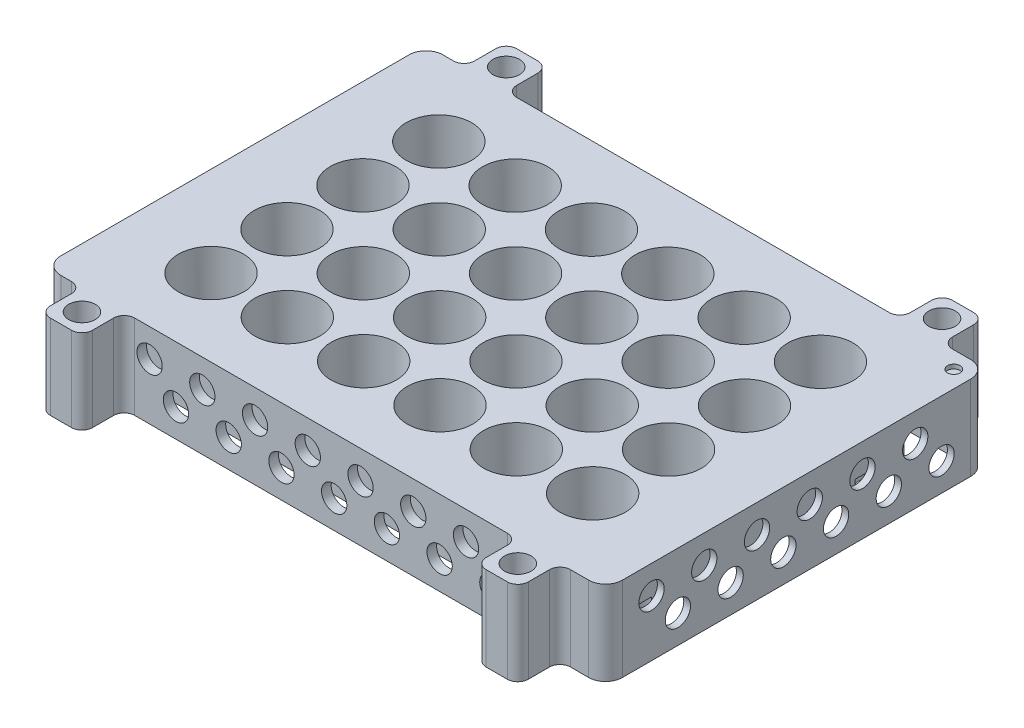
SolidWorks part; units mm, degrees
ref_plane "Front Plane" through (0, 0, 0) normal (0, 0, 1) x (1, 0, 0)
ref_plane "Top Plane" through (0, 0, 0) normal (0, 1, 0) x (1, 0, 0)
ref_plane "Right Plane" through (0, 0, 0) normal (1, 0, 0) x (0, 0, -1)
sketch "Sketch1" plane through (0, 0, 0) normal (0, 1, 0) x (1, 0, 0)
  line L1 (0, 0) -> (157.864, 0)
  line L2 (0, 0) -> (0, -90.551)
  line L3 (0, -90.551) -> (157.864, -90.551)
  line L4 (157.864, 0) -> (157.864, -90.551)
  dimension "D1" = 157.864
  dimension "D2" = 90.551
extrude "Boss-Extrude1" add sketch "Sketch1" along normal blind 24.5
sketch "Sketch39" plane through (0, 24.5, 0) normal (0, 1, 0) x (1, 0, 0)
  line L0 (37.0058, -18.5555) -> (30.949, -18.5555)
  line L1 (30.949, -18.5555) -> (30.4082, -19.0884)
  line L2 (30.4082, -19.0884) -> (30.4082, -25.1854)
  line L3 (30.4082, -25.1854) -> (37.0058, -25.1854)
  line L4 (37.0058, -18.5555) -> (37.0058, -25.1854)
  line L5 (30.4082, -25.1854) -> (37.0058, -18.5555) construction
  line L6 (55.0958, -11.3656) -> (49.039, -11.3656)
  line L7 (49.039, -11.3656) -> (48.4982, -11.8986)
  line L8 (48.4982, -11.8986) -> (48.4982, -17.9955)
  line L9 (48.4982, -17.9955) -> (55.0958, -17.9955)
  line L10 (55.0958, -11.3656) -> (55.0958, -17.9955)
  line L11 (48.4982, -17.9955) -> (55.0958, -11.3656) construction
  line L12 (73.1858, -11.3656) -> (67.129, -11.3656)
  line L13 (67.129, -11.3656) -> (66.5882, -11.8986)
  line L14 (66.5882, -11.8986) -> (66.5882, -17.9955)
  line L15 (66.5882, -17.9955) -> (73.1858, -17.9955)
  line L16 (73.1858, -11.3656) -> (73.1858, -17.9955)
  line L17 (66.5882, -17.9955) -> (73.1858, -11.3656) construction
  line L18 (91.2758, -11.3656) -> (85.219, -11.3656)
  line L19 (85.219, -11.3656) -> (84.6782, -11.8986)
  line L20 (84.6782, -11.8986) -> (84.6782, -17.9955)
  line L21 (84.6782, -17.9955) -> (91.2758, -17.9955)
  line L22 (91.2758, -11.3656) -> (91.2758, -17.9955)
  line L23 (84.6782, -17.9955) -> (91.2758, -11.3656) construction
  line L24 (109.3658, -11.3656) -> (103.309, -11.3656)
  line L25 (103.309, -11.3656) -> (102.7682, -11.8986)
  line L26 (102.7682, -11.8986) -> (102.7682, -17.9955)
  line L27 (102.7682, -17.9955) -> (109.3658, -17.9955)
  line L28 (109.3658, -11.3656) -> (109.3658, -17.9955)
  line L29 (102.7682, -17.9955) -> (109.3658, -11.3656) construction
  line L30 (127.4558, -11.3656) -> (121.399, -11.3656)
  line L31 (121.399, -11.3656) -> (120.8582, -11.8986)
  line L32 (120.8582, -11.8986) -> (120.8582, -17.9955)
  line L33 (120.8582, -17.9955) -> (127.4558, -17.9955)
  line L34 (127.4558, -11.3656) -> (127.4558, -17.9955)
  line L35 (120.8582, -17.9955) -> (127.4558, -11.3656) construction
  line L36 (55.0958, -29.3656) -> (49.039, -29.3656)
  line L37 (49.039, -29.3656) -> (48.4982, -29.8986)
  line L38 (48.4982, -29.8986) -> (48.4982, -35.9955)
  line L39 (48.4982, -35.9955) -> (55.0958, -35.9955)
  line L40 (55.0958, -29.3656) -> (55.0958, -35.9955)
  line L41 (48.4982, -35.9955) -> (55.0958, -29.3656) construction
  line L42 (73.1858, -29.3656) -> (67.129, -29.3656)
  line L43 (67.129, -29.3656) -> (66.5882, -29.8986)
  line L44 (66.5882, -29.8986) -> (66.5882, -35.9955)
  line L45 (66.5882, -35.9955) -> (73.1858, -35.9955)
  line L46 (73.1858, -29.3656) -> (73.1858, -35.9955)
  line L47 (66.5882, -35.9955) -> (73.1858, -29.3656) construction
  line L48 (91.2758, -29.3656) -> (85.219, -29.3656)
  line L49 (85.219, -29.3656) -> (84.6782, -29.8986)
  line L50 (84.6782, -29.8986) -> (84.6782, -35.9955)
  line L51 (84.6782, -35.9955) -> (91.2758, -35.9955)
  line L52 (91.2758, -29.3656) -> (91.2758, -35.9955)
  line L53 (84.6782, -35.9955) -> (91.2758, -29.3656) construction
  line L54 (109.3658, -29.3656) -> (103.309, -29.3656)
  line L55 (103.309, -29.3656) -> (102.7682, -29.8986)
  line L56 (102.7682, -29.8986) -> (102.7682, -35.9955)
  line L57 (102.7682, -35.9955) -> (109.3658, -35.9955)
  line L58 (109.3658, -29.3656) -> (109.3658, -35.9955)
  line L59 (102.7682, -35.9955) -> (109.3658, -29.3656) construction
  line L60 (127.4558, -29.3656) -> (121.399, -29.3656)
  line L61 (121.399, -29.3656) -> (120.8582, -29.8986)
  line L62 (120.8582, -29.8986) -> (120.8582, -35.9955)
  line L63 (120.8582, -35.9955) -> (127.4558, -35.9955)
  line L64 (127.4558, -29.3656) -> (127.4558, -35.9955)
  line L65 (120.8582, -35.9955) -> (127.4558, -29.3656) construction
  line L66 (55.0958, -47.3656) -> (49.039, -47.3656)
  line L67 (49.039, -47.3656) -> (48.4982, -47.8986)
  line L68 (48.4982, -47.8986) -> (48.4982, -53.9955)
  line L69 (48.4982, -53.9955) -> (55.0958, -53.9955)
  line L70 (55.0958, -47.3656) -> (55.0958, -53.9955)
  line L71 (48.4982, -53.9955) -> (55.0958, -47.3656) construction
  line L72 (73.1858, -47.3656) -> (67.129, -47.3656)
  line L73 (67.129, -47.3656) -> (66.5882, -47.8986)
  line L74 (66.5882, -47.8986) -> (66.5882, -53.9955)
  line L75 (66.5882, -53.9955) -> (73.1858, -53.9955)
  line L76 (73.1858, -47.3656) -> (73.1858, -53.9955)
  line L77 (66.5882, -53.9955) -> (73.1858, -47.3656) construction
  line L78 (91.2758, -47.3656) -> (85.219, -47.3656)
  line L79 (85.219, -47.3656) -> (84.6782, -47.8986)
  line L80 (84.6782, -47.8986) -> (84.6782, -53.9955)
  line L81 (84.6782, -53.9955) -> (91.2758, -53.9955)
  line L82 (91.2758, -47.3656) -> (91.2758, -53.9955)
  line L83 (84.6782, -53.9955) -> (91.2758, -47.3656) construction
  line L84 (109.3658, -47.3656) -> (103.309, -47.3656)
  line L85 (103.309, -47.3656) -> (102.7682, -47.8986)
  line L86 (102.7682, -47.8986) -> (102.7682, -53.9955)
  line L87 (102.7682, -53.9955) -> (109.3658, -53.9955)
  line L88 (109.3658, -47.3656) -> (109.3658, -53.9955)
  line L89 (102.7682, -53.9955) -> (109.3658, -47.3656) construction
  line L90 (127.4558, -47.3656) -> (121.399, -47.3656)
  line L91 (121.399, -47.3656) -> (120.8582, -47.8986)
  line L92 (120.8582, -47.8986) -> (120.8582, -53.9955)
  line L93 (120.8582, -53.9955) -> (127.4558, -53.9955)
  line L94 (127.4558, -47.3656) -> (127.4558, -53.9955)
  line L95 (120.8582, -53.9955) -> (127.4558, -47.3656) construction
  line L96 (55.0958, -65.3656) -> (49.039, -65.3656)
  line L97 (49.039, -65.3656) -> (48.4982, -65.8986)
  line L98 (48.4982, -65.8986) -> (48.4982, -71.9955)
  line L99 (48.4982, -71.9955) -> (55.0958, -71.9955)
  line L100 (55.0958, -65.3656) -> (55.0958, -71.9955)
  line L101 (48.4982, -71.9955) -> (55.0958, -65.3656) construction
  line L102 (73.1858, -65.3656) -> (67.129, -65.3656)
  line L103 (67.129, -65.3656) -> (66.5882, -65.8986)
  line L104 (66.5882, -65.8986) -> (66.5882, -71.9955)
  line L105 (66.5882, -71.9955) -> (73.1858, -71.9955)
  line L106 (73.1858, -65.3656) -> (73.1858, -71.9955)
  line L107 (66.5882, -71.9955) -> (73.1858, -65.3656) construction
  line L108 (91.2758, -65.3656) -> (85.219, -65.3656)
  line L109 (85.219, -65.3656) -> (84.6782, -65.8986)
  line L110 (84.6782, -65.8986) -> (84.6782, -71.9955)
  line L111 (84.6782, -71.9955) -> (91.2758, -71.9955)
  line L112 (91.2758, -65.3656) -> (91.2758, -71.9955)
  line L113 (84.6782, -71.9955) -> (91.2758, -65.3656) construction
  line L114 (109.3658, -65.3656) -> (103.309, -65.3656)
  line L115 (103.309, -65.3656) -> (102.7682, -65.8986)
  line L116 (102.7682, -65.8986) -> (102.7682, -71.9955)
  line L117 (102.7682, -71.9955) -> (109.3658, -71.9955)
  line L118 (109.3658, -65.3656) -> (109.3658, -71.9955)
  line L119 (102.7682, -71.9955) -> (109.3658, -65.3656) construction
  line L120 (127.4558, -65.3656) -> (121.399, -65.3656)
  line L121 (121.399, -65.3656) -> (120.8582, -65.8986)
  line L122 (120.8582, -65.8986) -> (120.8582, -71.9955)
  line L123 (120.8582, -71.9955) -> (127.4558, -71.9955)
  line L124 (127.4558, -65.3656) -> (127.4558, -71.9955)
  line L125 (120.8582, -71.9955) -> (127.4558, -65.3656) construction
  line L126 (37.0058, -29.3656) -> (30.949, -29.3656)
  line L127 (30.949, -29.3656) -> (30.4082, -29.8986)
  line L128 (30.4082, -29.8986) -> (30.4082, -35.9955)
  line L129 (30.4082, -35.9955) -> (37.0058, -35.9955)
  line L130 (37.0058, -29.3656) -> (37.0058, -35.9955)
  line L131 (30.4082, -35.9955) -> (37.0058, -29.3656) construction
  line L132 (37.0058, -47.3656) -> (30.949, -47.3656)
  line L133 (30.949, -47.3656) -> (30.4082, -47.8986)
  line L134 (30.4082, -47.8986) -> (30.4082, -53.9955)
  line L135 (30.4082, -53.9955) -> (37.0058, -53.9955)
  line L136 (37.0058, -47.3656) -> (37.0058, -53.9955)
  line L137 (30.4082, -53.9955) -> (37.0058, -47.3656) construction
  line L138 (37.0058, -65.3656) -> (30.949, -65.3656)
  line L139 (30.949, -65.3656) -> (30.4082, -65.8986)
  line L140 (30.4082, -65.8986) -> (30.4082, -71.9955)
  line L141 (30.4082, -71.9955) -> (37.0058, -71.9955)
  line L142 (37.0058, -65.3656) -> (37.0058, -71.9955)
  line L143 (30.4082, -71.9955) -> (37.0058, -65.3656) construction
  line L144 (37.0058, -11.3656) -> (30.949, -11.3656)
  line L145 (30.949, -11.3656) -> (30.4082, -11.8986)
  line L146 (30.4082, -11.8986) -> (30.4082, -17.9955)
  line L147 (30.4082, -17.9955) -> (37.0058, -17.9955)
  line L148 (37.0058, -11.3656) -> (37.0058, -17.9955)
  line L149 (30.4082, -17.9955) -> (37.0058, -11.3656) construction
  line L150 (48.4982, -25.1854) -> (55.0958, -25.1854)
  line L151 (55.0958, -18.5555) -> (55.0958, -25.1854)
  line L152 (55.0958, -18.5555) -> (49.039, -18.5555)
  line L153 (49.039, -18.5555) -> (48.4982, -19.0884)
  line L154 (48.4982, -19.0884) -> (48.4982, -25.1854)
  line L155 (48.4982, -25.1854) -> (55.0958, -18.5555) construction
  line L156 (66.5882, -25.1854) -> (73.1858, -25.1854)
  line L157 (73.1858, -18.5555) -> (73.1858, -25.1854)
  line L158 (73.1858, -18.5555) -> (67.129, -18.5555)
  line L159 (67.129, -18.5555) -> (66.5882, -19.0884)
  line L160 (66.5882, -19.0884) -> (66.5882, -25.1854)
  line L161 (66.5882, -25.1854) -> (73.1858, -18.5555) construction
  line L162 (84.6782, -25.1854) -> (91.2758, -25.1854)
  line L163 (91.2758, -18.5555) -> (91.2758, -25.1854)
  line L164 (91.2758, -18.5555) -> (85.219, -18.5555)
  line L165 (85.219, -18.5555) -> (84.6782, -19.0884)
  line L166 (84.6782, -19.0884) -> (84.6782, -25.1854)
  line L167 (84.6782, -25.1854) -> (91.2758, -18.5555) construction
  line L168 (102.7682, -25.1854) -> (109.3658, -25.1854)
  line L169 (109.3658, -18.5555) -> (109.3658, -25.1854)
  line L170 (109.3658, -18.5555) -> (103.309, -18.5555)
  line L171 (103.309, -18.5555) -> (102.7682, -19.0884)
  line L172 (102.7682, -19.0884) -> (102.7682, -25.1854)
  line L173 (102.7682, -25.1854) -> (109.3658, -18.5555) construction
  line L174 (120.8582, -25.1854) -> (127.4558, -25.1854)
  line L175 (127.4558, -18.5555) -> (127.4558, -25.1854)
  line L176 (127.4558, -18.5555) -> (121.399, -18.5555)
  line L177 (121.399, -18.5555) -> (120.8582, -19.0884)
  line L178 (120.8582, -19.0884) -> (120.8582, -25.1854)
  line L179 (120.8582, -25.1854) -> (127.4558, -18.5555) construction
  line L180 (48.4982, -43.1854) -> (55.0958, -43.1854)
  line L181 (55.0958, -36.5555) -> (55.0958, -43.1854)
  line L182 (55.0958, -36.5555) -> (49.039, -36.5555)
  line L183 (49.039, -36.5555) -> (48.4982, -37.0884)
  line L184 (48.4982, -37.0884) -> (48.4982, -43.1854)
  line L185 (48.4982, -43.1854) -> (55.0958, -36.5555) construction
  line L186 (66.5882, -43.1854) -> (73.1858, -43.1854)
  line L187 (73.1858, -36.5555) -> (73.1858, -43.1854)
  line L188 (73.1858, -36.5555) -> (67.129, -36.5555)
  line L189 (67.129, -36.5555) -> (66.5882, -37.0884)
  line L190 (66.5882, -37.0884) -> (66.5882, -43.1854)
  line L191 (66.5882, -43.1854) -> (73.1858, -36.5555) construction
  line L192 (84.6782, -43.1854) -> (91.2758, -43.1854)
  line L193 (91.2758, -36.5555) -> (91.2758, -43.1854)
  line L194 (91.2758, -36.5555) -> (85.219, -36.5555)
  line L195 (85.219, -36.5555) -> (84.6782, -37.0884)
  line L196 (84.6782, -37.0884) -> (84.6782, -43.1854)
  line L197 (84.6782, -43.1854) -> (91.2758, -36.5555) construction
  line L198 (102.7682, -43.1854) -> (109.3658, -43.1854)
  line L199 (109.3658, -36.5555) -> (109.3658, -43.1854)
  line L200 (109.3658, -36.5555) -> (103.309, -36.5555)
  line L201 (103.309, -36.5555) -> (102.7682, -37.0884)
  line L202 (102.7682, -37.0884) -> (102.7682, -43.1854)
  line L203 (102.7682, -43.1854) -> (109.3658, -36.5555) construction
  line L204 (120.8582, -43.1854) -> (127.4558, -43.1854)
  line L205 (127.4558, -36.5555) -> (127.4558, -43.1854)
  line L206 (127.4558, -36.5555) -> (121.399, -36.5555)
  line L207 (121.399, -36.5555) -> (120.8582, -37.0884)
  line L208 (120.8582, -37.0884) -> (120.8582, -43.1854)
  line L209 (120.8582, -43.1854) -> (127.4558, -36.5555) construction
  line L210 (48.4982, -61.1854) -> (55.0958, -61.1854)
  line L211 (55.0958, -54.5555) -> (55.0958, -61.1854)
  line L212 (55.0958, -54.5555) -> (49.039, -54.5555)
  line L213 (49.039, -54.5555) -> (48.4982, -55.0884)
  line L214 (48.4982, -55.0884) -> (48.4982, -61.1854)
  line L215 (48.4982, -61.1854) -> (55.0958, -54.5555) construction
  line L216 (66.5882, -61.1854) -> (73.1858, -61.1854)
  line L217 (73.1858, -54.5555) -> (73.1858, -61.1854)
  line L218 (73.1858, -54.5555) -> (67.129, -54.5555)
  line L219 (67.129, -54.5555) -> (66.5882, -55.0884)
  line L220 (66.5882, -55.0884) -> (66.5882, -61.1854)
  line L221 (66.5882, -61.1854) -> (73.1858, -54.5555) construction
  line L222 (84.6782, -61.1854) -> (91.2758, -61.1854)
  line L223 (91.2758, -54.5555) -> (91.2758, -61.1854)
  line L224 (91.2758, -54.5555) -> (85.219, -54.5555)
  line L225 (85.219, -54.5555) -> (84.6782, -55.0884)
  line L226 (84.6782, -55.0884) -> (84.6782, -61.1854)
  line L227 (84.6782, -61.1854) -> (91.2758, -54.5555) construction
  line L228 (102.7682, -61.1854) -> (109.3658, -61.1854)
  line L229 (109.3658, -54.5555) -> (109.3658, -61.1854)
  line L230 (109.3658, -54.5555) -> (103.309, -54.5555)
  line L231 (103.309, -54.5555) -> (102.7682, -55.0884)
  line L232 (102.7682, -55.0884) -> (102.7682, -61.1854)
  line L233 (102.7682, -61.1854) -> (109.3658, -54.5555) construction
  line L234 (120.8582, -61.1854) -> (127.4558, -61.1854)
  line L235 (127.4558, -54.5555) -> (127.4558, -61.1854)
  line L236 (127.4558, -54.5555) -> (121.399, -54.5555)
  line L237 (121.399, -54.5555) -> (120.8582, -55.0884)
  line L238 (120.8582, -55.0884) -> (120.8582, -61.1854)
  line L239 (120.8582, -61.1854) -> (127.4558, -54.5555) construction
  line L240 (48.4982, -79.1854) -> (55.0958, -79.1854)
  line L241 (55.0958, -72.5555) -> (55.0958, -79.1854)
  line L242 (55.0958, -72.5555) -> (49.039, -72.5555)
  line L243 (49.039, -72.5555) -> (48.4982, -73.0884)
  line L244 (48.4982, -73.0884) -> (48.4982, -79.1854)
  line L245 (48.4982, -79.1854) -> (55.0958, -72.5555) construction
  line L246 (66.5882, -79.1854) -> (73.1858, -79.1854)
  line L247 (73.1858, -72.5555) -> (73.1858, -79.1854)
  line L248 (73.1858, -72.5555) -> (67.129, -72.5555)
  line L249 (67.129, -72.5555) -> (66.5882, -73.0884)
  line L250 (66.5882, -73.0884) -> (66.5882, -79.1854)
  line L251 (66.5882, -79.1854) -> (73.1858, -72.5555) construction
  line L252 (84.6782, -79.1854) -> (91.2758, -79.1854)
  line L253 (91.2758, -72.5555) -> (91.2758, -79.1854)
  line L254 (91.2758, -72.5555) -> (85.219, -72.5555)
  line L255 (85.219, -72.5555) -> (84.6782, -73.0884)
  line L256 (84.6782, -73.0884) -> (84.6782, -79.1854)
  line L257 (84.6782, -79.1854) -> (91.2758, -72.5555) construction
  line L258 (102.7682, -79.1854) -> (109.3658, -79.1854)
  line L259 (109.3658, -72.5555) -> (109.3658, -79.1854)
  line L260 (109.3658, -72.5555) -> (103.309, -72.5555)
  line L261 (103.309, -72.5555) -> (102.7682, -73.0884)
  line L262 (102.7682, -73.0884) -> (102.7682, -79.1854)
  line L263 (102.7682, -79.1854) -> (109.3658, -72.5555) construction
  line L264 (120.8582, -79.1854) -> (127.4558, -79.1854)
  line L265 (127.4558, -72.5555) -> (127.4558, -79.1854)
  line L266 (127.4558, -72.5555) -> (121.399, -72.5555)
  line L267 (121.399, -72.5555) -> (120.8582, -73.0884)
  line L268 (120.8582, -73.0884) -> (120.8582, -79.1854)
  line L269 (120.8582, -79.1854) -> (127.4558, -72.5555) construction
  line L270 (30.4082, -43.1854) -> (37.0058, -43.1854)
  line L271 (37.0058, -36.5555) -> (37.0058, -43.1854)
  line L272 (37.0058, -36.5555) -> (30.949, -36.5555)
  line L273 (30.949, -36.5555) -> (30.4082, -37.0884)
  line L274 (30.4082, -37.0884) -> (30.4082, -43.1854)
  line L275 (30.4082, -43.1854) -> (37.0058, -36.5555) construction
  line L276 (30.4082, -61.1854) -> (37.0058, -61.1854)
  line L277 (37.0058, -54.5555) -> (37.0058, -61.1854)
  line L278 (37.0058, -54.5555) -> (30.949, -54.5555)
  line L279 (30.949, -54.5555) -> (30.4082, -55.0884)
  line L280 (30.4082, -55.0884) -> (30.4082, -61.1854)
  line L281 (30.4082, -61.1854) -> (37.0058, -54.5555) construction
  line L282 (30.4082, -79.1854) -> (37.0058, -79.1854)
  line L283 (37.0058, -72.5555) -> (37.0058, -79.1854)
  line L284 (37.0058, -72.5555) -> (30.949, -72.5555)
  line L285 (30.949, -72.5555) -> (30.4082, -73.0884)
  line L286 (30.4082, -73.0884) -> (30.4082, -79.1854)
  line L287 (30.4082, -79.1854) -> (37.0058, -72.5555) construction
  line L288 (127.4558, -25.1854) -> (157.864, -25.1854) construction
  line L289 (30.4082, -79.1854) -> (0, -79.1854) construction
  line L290 (0, 0) -> (0, -90.551) construction
  line L291 (30.4082, -79.1854) -> (30.4082, -90.551) construction
  line L292 (0, -90.551) -> (157.864, -90.551) construction
  line L293 (127.4558, -11.3656) -> (127.4558, 0) construction
  line L294 (157.864, 0) -> (0, 0) construction
  line L295 (127.4558, -11.3656) -> (157.864, -11.3656) construction
  line L296 (157.864, -90.551) -> (157.864, 0) construction
  point P0 (33.707, -21.8704)
  point P2 (33.707, -14.6806)
  point P12 (51.797, -14.6806)
  point P18 (69.887, -14.6806)
  point P24 (87.977, -14.6806)
  point P30 (106.067, -14.6806)
  point P36 (124.157, -14.6806)
  point P42 (51.797, -32.6806)
  point P48 (69.887, -32.6806)
  point P54 (87.977, -32.6806)
  point P60 (106.067, -32.6806)
  point P66 (124.157, -32.6806)
  point P72 (51.797, -50.6806)
  point P78 (69.887, -50.6806)
  point P84 (87.977, -50.6806)
  point P90 (106.067, -50.6806)
  point P96 (124.157, -50.6806)
  point P102 (51.797, -68.6806)
  point P108 (69.887, -68.6806)
  point P114 (87.977, -68.6806)
  point P120 (106.067, -68.6806)
  point P126 (124.157, -68.6806)
  point P132 (33.707, -32.6806)
  point P138 (33.707, -50.6806)
  point P144 (33.707, -68.6806)
  point P153 (51.797, -21.8704)
  point P159 (69.887, -21.8704)
  point P165 (87.977, -21.8704)
  point P171 (106.067, -21.8704)
  point P177 (124.157, -21.8704)
  point P183 (51.797, -39.8704)
  point P189 (69.887, -39.8704)
  point P195 (87.977, -39.8704)
  point P201 (106.067, -39.8704)
  point P207 (124.157, -39.8704)
  point P213 (51.797, -57.8704)
  point P219 (69.887, -57.8704)
  point P225 (87.977, -57.8704)
  point P231 (106.067, -57.8704)
  point P237 (124.157, -57.8704)
  point P243 (51.797, -75.8704)
  point P249 (69.887, -75.8704)
  point P255 (87.977, -75.8704)
  point P261 (106.067, -75.8704)
  point P267 (124.157, -75.8704)
  point P273 (33.707, -39.8704)
  point P279 (33.707, -57.8704)
  point P285 (33.707, -75.8704)
  dimension "D2" = 6.0568
  dimension "D3" = 6.0969
  dimension "D4" = 6.5976
  dimension "D5" = 6.6299
  dimension "D6" = 0.7593
  dimension "D7" = 6
  dimension "D8" = 4
  dimension "D9" = 0.56
  dimension "D10" = 6.0568
  dimension "D11" = 6.0969
  dimension "D12" = 6.6299
  dimension "D13" = 6.5976
  dimension "D14" = 0.7593
  dimension "D15" = 6
  dimension "D16" = 4
extrude "Cut-Extrude30" cut sketch "Sketch39" against normal up to surface (24.5 mm away) up to face at (78.932, 0, 45.2755)
sketch "Sketch7" plane through (0, 0, 0) normal (0, -1, 0) x (1, 0, 0)
  line L0 (124.157, 18.2755) -> (157.864, 18.2755) construction
  line L1 (157.864, 90.551) -> (157.864, 0) construction
  line L2 (124.157, 18.2755) -> (124.157, 0) construction
  line L3 (157.864, 0) -> (0, 0) construction
  line L4 (33.707, 18.2755) -> (0, 18.2755) construction
  line L5 (0, 0) -> (0, 90.551) construction
  line L6 (33.707, 72.2755) -> (33.707, 90.551) construction
  line L7 (0, 90.551) -> (157.864, 90.551) construction
  line L8 (33.707, 72.2755) -> (33.707, 90.551) construction
  circle A0 centre (33.707, 72.2755) radius 7.75
  circle A2 centre (51.797, 72.2755) radius 7.75
  circle A3 centre (69.887, 72.2755) radius 7.75
  circle A4 centre (87.977, 72.2755) radius 7.75
  circle A5 centre (106.067, 72.2755) radius 7.75
  circle A6 centre (124.157, 72.2755) radius 7.75
  circle A7 centre (51.797, 54.2755) radius 7.75
  circle A8 centre (69.887, 54.2755) radius 7.75
  circle A9 centre (87.977, 54.2755) radius 7.75
  circle A10 centre (106.067, 54.2755) radius 7.75
  circle A11 centre (124.157, 54.2755) radius 7.75
  circle A12 centre (51.797, 36.2755) radius 7.75
  circle A13 centre (69.887, 36.2755) radius 7.75
  circle A14 centre (87.977, 36.2755) radius 7.75
  circle A15 centre (106.067, 36.2755) radius 7.75
  circle A16 centre (124.157, 36.2755) radius 7.75
  circle A17 centre (51.797, 18.2755) radius 7.75
  circle A18 centre (69.887, 18.2755) radius 7.75
  circle A19 centre (87.977, 18.2755) radius 7.75
  circle A20 centre (106.067, 18.2755) radius 7.75
  circle A21 centre (124.157, 18.2755) radius 7.75
  circle A22 centre (33.707, 54.2755) radius 7.75
  circle A23 centre (33.707, 36.2755) radius 7.75
  circle A24 centre (33.707, 18.2755) radius 7.75
  dimension "D1" = 15.5
  dimension "D6" = 18
  dimension "D3" = 18.09
  dimension "D4" = 18
  dimension "D5" = 18.09
  dimension "D7" = 6
  dimension "D8" = 4
extrude "Cut-Extrude5" cut sketch "Sketch7" along normal blind 17 from surface starting at face at (33.1554, 24.5, 75.314)
sketch "Sketch23" plane through (0, 24.5, 0) normal (0, 1, 0) x (1, 0, 0)
  line L0 (0, -90.551) -> (157.864, -90.551) construction
  line L1 (143.5751, -88.6374) -> (14.2889, -88.6374)
  line L2 (143.5751, -88.6374) -> (143.5751, -1.9136)
  line L3 (143.5751, -1.9136) -> (14.2889, -1.9136)
  line L4 (14.2889, -88.6374) -> (14.2889, -1.9136)
  line L5 (134.6751, -82.6374) -> (23.1889, -82.6374)
  line L6 (134.6751, -82.6374) -> (134.6751, -7.9136)
  line L7 (134.6751, -7.9136) -> (23.1889, -7.9136)
  line L8 (23.1889, -82.6374) -> (23.1889, -7.9136)
  line L9 (157.864, -90.551) -> (157.864, 0) construction
  line L10 (157.864, 0) -> (0, 0) construction
  line L11 (0, 0) -> (0, -90.551) construction
  point P8 (157.864, -45.2755)
  point P17 (0, -45.2755)
  dimension "D1" = 129.2861
  dimension "D2" = 8.9
  dimension "D3" = 8.9
  dimension "D4" = 6
  dimension "D5" = 6
  dimension "D6" = 14.2889
  dimension "D8" = 1.9136
  dimension "D9" = 86.7238
  dimension "D10" = 1.9136
  dimension "D11" = 14.2889
extrude "Cut-Extrude21" cut sketch "Sketch23" against normal blind 4.5
fillet "Fillet7" radius 1 4 edges at (134.6751, 22.25, 7.9136) (23.1889, 22.25, 7.9136) (23.1889, 22.25, 82.6374) (134.6751, 22.25, 82.6374)
fillet "Fillet8" radius 2.75 4 edges at (143.5751, 22.25, 1.9136) (14.2889, 22.25, 1.9136) (14.2889, 22.25, 88.6374) (143.5751, 22.25, 88.6374)
sketch "Sketch26" plane through (0, 24.5, 0) normal (0, 1, 0) x (1, 0, 0)
  line L1 (18.0889, -82.6374) -> (134.6751, -82.6374)
  line L2 (18.0889, -82.6374) -> (18.0889, -7.9136)
  line L3 (18.0889, -7.9136) -> (134.6751, -7.9136)
  line L4 (134.6751, -82.6374) -> (134.6751, -7.9136)
  dimension "D1" = 0
  dimension "D2" = 0
  dimension "D3" = 1
  dimension "D4" = 0
extrude "Cut-Extrude22" cut sketch "Sketch26" against normal blind 3
sketch "Sketch29" plane through (0, 24.5, 0) normal (0, 1, 0) x (1, 0, 0)
  line L0 (157.864, 0) -> (0, 0) construction
  line L1 (157.864, -90.551) -> (145.4887, -90.551)
  line L2 (157.864, -90.551) -> (157.864, 0)
  line L3 (157.864, 0) -> (145.4887, 0)
  line L4 (145.4887, -90.551) -> (145.4887, 0)
  line L6 (0, -90.551) -> (12.3753, -90.551)
  line L7 (0, -90.551) -> (0, 0)
  line L8 (0, 0) -> (12.3753, 0)
  line L9 (12.3753, -90.551) -> (12.3753, 0)
  dimension "D2" = 1.9136
  dimension "D3" = 1.9136
extrude "Cut-Extrude25" cut sketch "Sketch29" against normal through all
fillet "Fillet9" radius 4 4 edges at (12.3753, 12.25, 90.551) (145.4887, 12.25, 90.551) (145.4887, 12.25, 0) (12.3753, 12.25, 0)
sketch "Sketch30" plane through (0, 0, 0) normal (0, -1, 0) x (1, 0, 0)
  line L0 (141.4887, 0) -> (16.3753, 0) construction
  line L1 (134.6936, 0) -> (124.6936, 0)
  line L2 (134.6936, 0) -> (134.6936, -10)
  line L3 (134.6936, -10) -> (124.6936, -10)
  line L4 (124.6936, 0) -> (124.6936, -10)
  line L5 (16.3753, 90.551) -> (141.4887, 90.551) construction
  line L6 (21.3936, 0) -> (31.3936, 0)
  line L7 (21.3936, 0) -> (21.3936, -10)
  line L8 (21.3936, -10) -> (31.3936, -10)
  line L9 (31.3936, 0) -> (31.3936, -10)
  line L10 (134.6936, 90.551) -> (124.6936, 90.551)
  line L11 (134.6936, 90.551) -> (134.6936, 100.551)
  line L12 (134.6936, 100.551) -> (124.6936, 100.551)
  line L13 (124.6936, 90.551) -> (124.6936, 100.551)
  line L14 (124.6936, -10) -> (31.3936, -10) construction
  line L15 (21.3936, 90.551) -> (31.3936, 90.551)
  line L16 (21.3936, 90.551) -> (21.3936, 100.551)
  line L17 (21.3936, 100.551) -> (31.3936, 100.551)
  line L18 (31.3936, 90.551) -> (31.3936, 100.551)
  line L19 (124.6936, 100.551) -> (31.3936, 100.551) construction
  line L20 (31.3936, -10) -> (21.3936, 0) construction
  line L22 (33.707, 0) -> (31.3936, 0) construction
  line L23 (21.3936, 90.551) -> (16.3753, 90.551) construction
  line L24 (33.707, 72.2755) -> (33.707, 18.2755) construction
  line L25 (33.707, 18.2755) -> (33.707, 0) construction
  line L26 (21.3936, -10) -> (31.3936, 0) construction
  line L27 (33.707, 72.2755) -> (33.707, 90.551) construction
  line L28 (31.3936, 90.551) -> (21.3936, 100.551) construction
  line L29 (21.3936, 90.551) -> (31.3936, 100.551) construction
  point P21 (26.3936, -5)
  point P25 (26.3936, 95.551)
  dimension "D1" = 10
  dimension "D2" = 93.3
  dimension "D3" = 7.3134
  dimension "D4" = 7.3134
extrude "Boss-Extrude2" add sketch "Sketch30" against normal through all
sketch "Sketch31" plane through (0, 24.5, 0) normal (0, 1, 0) x (1, 0, 0)
  line L0 (21.3936, 10) -> (31.3936, 0) construction
  line L1 (31.3936, 0) -> (21.3936, 0) construction
  line L2 (21.3936, 0) -> (31.3936, 10) construction
  line L3 (124.6936, 10) -> (134.6936, 0) construction
  line L4 (134.6936, 0) -> (124.6936, 0) construction
  line L5 (124.6936, 0) -> (134.6936, 10) construction
  line L6 (124.6936, -90.551) -> (134.6936, -100.551) construction
  line L7 (134.6936, -100.551) -> (124.6936, -100.551) construction
  line L8 (124.6936, -100.551) -> (134.6936, -90.551) construction
  line L9 (21.3936, -90.551) -> (31.3936, -100.551) construction
  line L10 (31.3936, -100.551) -> (21.3936, -100.551) construction
  line L11 (21.3936, -100.551) -> (31.3936, -90.551) construction
  circle A0 centre (26.3936, 5) radius 3.15
  circle A1 centre (129.6936, 5) radius 3.15
  circle A2 centre (26.3936, -95.551) radius 3.15
  circle A3 centre (129.6936, -95.551) radius 3.15
  dimension "D1" = 6.3
extrude "Cut-Extrude26" cut sketch "Sketch31" against normal through all
fillet "Fillet10" radius 2.5 16 edges at (21.3936, 12.25, 100.551) (124.6936, 12.25, 100.551) (31.3936, 12.25, 100.551) (134.6936, 12.25, 100.551) (134.6936, 12.25, -10) (124.6936, 12.25, -10) (31.3936, 12.25, -10) (21.3936, 12.25, -10) (21.3936, 12.25, 90.551) (31.3936, 12.25, 90.551) (124.6936, 12.25, 90.551) (134.6936, 12.25, 90.551) (134.6936, 12.25, 0) (124.6936, 12.25, 0) (31.3936, 12.25, 0) (21.3936, 12.25, 0)
sketch "Sketch35" plane through (0, 21.5, 0) normal (0, 1, 0) x (1, 0, 0)
  line L0 (33.707, -54.2755) -> (51.797, -72.2755) construction
  line L1 (51.797, -72.2755) -> (33.707, -72.2755) construction
  line L2 (33.707, -72.2755) -> (51.797, -54.2755) construction
  line L3 (106.067, -18.2755) -> (124.157, -36.2755) construction
  line L4 (124.157, -36.2755) -> (106.067, -36.2755) construction
  line L5 (106.067, -36.2755) -> (124.157, -18.2755) construction
  circle A2 centre (115.112, -27.2755) radius 1.4
  circle A3 centre (42.752, -63.2755) radius 1.4
  dimension "D1" = 2.8
extrude "Boss-Extrude3" add sketch "Sketch35" along normal blind 0.75
sketch "Sketch37" plane through (0, 24.5, 0) normal (0, 1, 0) x (1, 0, 0)
  line L1 (-21.3738, -118.5753) -> (214.6608, -118.5753)
  line L2 (-21.3738, -118.5753) -> (-21.3738, 29.3482)
  line L3 (-21.3738, 29.3482) -> (214.6608, 29.3482)
  line L4 (214.6608, -118.5753) -> (214.6608, 29.3482)
extrude "Cut-Extrude29" cut sketch "Sketch37" against normal blind 4.5
sketch "Sketch36" plane through (0, 0, 0) normal (0, -1, 0) x (1, 0, 0)
  line L0 (23.3443, 83.2148) -> (23.3443, 88.2648) construction
  line L1 (14.5962, 88.2648) -> (143.8803, 88.2648)
  line L2 (14.5962, 88.2648) -> (14.5962, 2.0921)
  line L3 (14.5962, 2.0921) -> (143.8803, 2.0921)
  line L4 (143.8803, 88.2648) -> (143.8803, 2.0921)
  line L5 (23.3443, 83.2148) -> (135.1322, 83.2148)
  line L6 (23.3443, 83.2148) -> (23.3443, 7.142)
  line L7 (23.3443, 7.142) -> (135.1322, 7.142)
  line L8 (135.1322, 83.2148) -> (135.1322, 7.142)
  line L9 (23.3443, 83.2148) -> (14.5962, 83.2148) construction
  line L10 (135.1322, 7.142) -> (143.8803, 7.142) construction
  line L11 (135.1322, 7.142) -> (135.1322, 2.0921) construction
extrude "Cut-Extrude28" cut sketch "Sketch36" against normal blind 17
fillet "Fillet11" radius 4 4 edges at (135.1322, 8.5, 83.2148) (23.3443, 8.5, 83.2148) (23.3443, 8.5, 7.142) (135.1322, 8.5, 7.142)
fillet "Fillet12" radius 4 4 edges at (143.8803, 8.5, 88.2648) (14.5962, 8.5, 88.2648) (14.5962, 8.5, 2.0921) (143.8803, 8.5, 2.0921)
sketch "Sketch42" plane through (0, 0, 0) normal (0, -1, 0) x (1, 0, 0)
  line L0 (22.1833, 72.1734) -> (22.1833, 18.1834) construction
  line L1 (22.1833, 18.1834) -> (136.2933, 18.1834) construction
  line L2 (136.2933, 18.1834) -> (136.2933, 72.1734) construction
  line L3 (136.2933, 72.1734) -> (22.1833, 72.1734) construction
  line L4 (22.1833, 72.1734) -> (14.5962, 72.1734) construction
  line L5 (14.5962, 84.2648) -> (14.5962, 6.0921) construction
  line L6 (22.1833, 72.1734) -> (22.1833, 88.2648) construction
  line L7 (139.8803, 88.2648) -> (18.5962, 88.2648) construction
  line L8 (136.2933, 72.1734) -> (143.8803, 72.1734) construction
  line L9 (143.8803, 6.0921) -> (143.8803, 84.2648) construction
  line L10 (136.2933, 18.1834) -> (136.2933, 2.0921) construction
  line L11 (18.5962, 2.0921) -> (139.8803, 2.0921) construction
  circle A0 centre (22.1833, 72.1734) radius 3.1
  circle A1 centre (22.1833, 18.1834) radius 3.1
  circle A2 centre (136.2933, 18.1834) radius 3.1
  circle A3 centre (136.2933, 72.1734) radius 3.1
  dimension "D1" = 6.2
  dimension "D2" = 114.11
  dimension "D3" = 53.99
extrude "Cut-Extrude31" cut sketch "Sketch42" against normal blind 2.75
sketch "Sketch43" plane through (0, 20, 0) normal (0, 1, 0) x (1, 0, 0)
  circle A0 centre (141.4887, -4) radius 1.5
  arc A1 (145.4887, -4) -> (141.4887, 0) centre (141.4887, -4) ccw construction
  dimension "D1" = 3
extrude "Cut-Extrude32" cut sketch "Sketch43" against normal blind 1
chamfer "Chamfer1" [suppressed] distance 0.25 angle 45
sketch "Sketch44" plane through (12.3753, 0, 0) normal (-1, 0, 0) x (0, 0, 1)
  line L0 (10.9005, 6.6667) -> (23.4005, 6.6667) construction
  line L1 (23.4005, 6.6667) -> (35.9005, 6.6667) construction
  line L2 (35.9005, 6.6667) -> (48.4005, 6.6667) construction
  line L3 (48.4005, 6.6667) -> (60.9005, 6.6667) construction
  line L4 (60.9005, 6.6667) -> (73.4005, 6.6667) construction
  line L5 (17.1505, 13.3333) -> (29.6505, 13.3333) construction
  line L6 (29.6505, 13.3333) -> (42.1505, 13.3333) construction
  line L7 (42.1505, 13.3333) -> (54.6505, 13.3333) construction
  line L8 (54.6505, 13.3333) -> (67.1505, 13.3333) construction
  line L9 (67.1505, 13.3333) -> (79.6505, 13.3333) construction
  line L10 (10.9005, 6.6667) -> (17.1505, 13.3333) construction
  line L11 (17.1505, 13.3333) -> (23.4005, 6.6667) construction
  line L12 (10.9005, 6.6667) -> (4, 6.6667) construction
  line L13 (4, 20) -> (4, 0) construction
  line L14 (79.6505, 13.3333) -> (86.551, 13.3333) construction
  line L15 (86.551, 0) -> (86.551, 20) construction
  line L16 (17.1505, 13.3333) -> (17.1505, 20) construction
  line L17 (86.551, 20) -> (4, 20) construction
  line L18 (10.9005, 6.6667) -> (10.9005, 0) construction
  line L19 (86.551, 0) -> (4, 0) construction
  line L20 (17.1505, 13.3333) -> (17.1505, 6.6667) construction
  circle A0 centre (10.9005, 6.6667) radius 3
  circle A1 centre (23.4005, 6.6667) radius 3
  circle A2 centre (35.9005, 6.6667) radius 3
  circle A3 centre (48.4005, 6.6667) radius 3
  circle A4 centre (60.9005, 6.6667) radius 3
  circle A5 centre (73.4005, 6.6667) radius 3
  circle A6 centre (17.1505, 13.3333) radius 3
  circle A7 centre (29.6505, 13.3333) radius 3
  circle A8 centre (42.1505, 13.3333) radius 3
  circle A9 centre (54.6505, 13.3333) radius 3
  circle A10 centre (67.1505, 13.3333) radius 3
  circle A11 centre (79.6505, 13.3333) radius 3
  dimension "D1" = 6
  dimension "D2" = 12.5
extrude "Cut-Extrude33" cut sketch "Sketch44" against normal up to surface (2.2209 mm away) up to face at (14.5962, 8.5, 45.1784)
sketch "Sketch45" plane through (0, 0, 90.551) normal (0, 0, 1) x (1, 0, 0)
  line L0 (37.4186, 13.3333) -> (49.9186, 13.3333) construction
  line L1 (49.9186, 13.3333) -> (62.4186, 13.3333) construction
  line L2 (62.4186, 13.3333) -> (74.9186, 13.3333) construction
  line L3 (74.9186, 13.3333) -> (87.4186, 13.3333) construction
  line L4 (87.4186, 13.3333) -> (99.9186, 13.3333) construction
  line L5 (99.9186, 13.3333) -> (112.4186, 13.3333) construction
  line L6 (118.6686, 6.6667) -> (106.1686, 6.6667) construction
  line L7 (106.1686, 6.6667) -> (93.6686, 6.6667) construction
  line L8 (93.6686, 6.6667) -> (81.1686, 6.6667) construction
  line L9 (81.1686, 6.6667) -> (68.6686, 6.6667) construction
  line L10 (68.6686, 6.6667) -> (56.1686, 6.6667) construction
  line L11 (56.1686, 6.6667) -> (43.6686, 6.6667) construction
  line L12 (43.6686, 6.6667) -> (37.4186, 13.3333) construction
  line L13 (37.4186, 13.3333) -> (49.9186, 13.3333) construction
  line L14 (49.9186, 13.3333) -> (43.6686, 6.6667) construction
  line L15 (37.4186, 13.3333) -> (37.4186, 20) construction
  line L16 (122.1936, 20) -> (33.8936, 20) construction
  line L17 (43.6686, 6.6667) -> (43.6686, 0) construction
  line L18 (33.8936, 0) -> (122.1936, 0) construction
  line L19 (37.4186, 13.3333) -> (33.8936, 13.3333) construction
  line L20 (33.8936, 20) -> (33.8936, 0) construction
  line L21 (118.6686, 6.6667) -> (122.1936, 6.6667) construction
  line L22 (122.1936, 0) -> (122.1936, 20) construction
  line L23 (43.6686, 6.6667) -> (43.6686, 13.3333) construction
  circle A0 centre (37.4186, 13.3333) radius 3
  circle A1 centre (49.9186, 13.3333) radius 3
  circle A2 centre (62.4186, 13.3333) radius 3
  circle A3 centre (74.9186, 13.3333) radius 3
  circle A4 centre (87.4186, 13.3333) radius 3
  circle A5 centre (99.9186, 13.3333) radius 3
  circle A6 centre (112.4186, 13.3333) radius 3
  circle A7 centre (43.6686, 6.6667) radius 3
  circle A8 centre (56.1686, 6.6667) radius 3
  circle A9 centre (68.6686, 6.6667) radius 3
  circle A10 centre (81.1686, 6.6667) radius 3
  circle A11 centre (93.6686, 6.6667) radius 3
  circle A12 centre (106.1686, 6.6667) radius 3
  circle A13 centre (118.6686, 6.6667) radius 3
  dimension "D1" = 6
  dimension "D2" = 12.5
extrude "Cut-Extrude34" cut sketch "Sketch45" against normal up to surface (2.2862 mm away) up to face at (79.2383, 8.5, 88.2648)
sketch "Sketch46" plane through (145.4887, 0, 0) normal (1, 0, 0) x (0, 0, -1)
  line L0 (-79.6505, 13.3333) -> (-67.1505, 13.3333) construction
  line L1 (-67.1505, 13.3333) -> (-54.6505, 13.3333) construction
  line L2 (-54.6505, 13.3333) -> (-42.1505, 13.3333) construction
  line L3 (-42.1505, 13.3333) -> (-29.6505, 13.3333) construction
  line L4 (-29.6505, 13.3333) -> (-17.1505, 13.3333) construction
  line L5 (-73.4005, 6.6667) -> (-60.9005, 6.6667) construction
  line L6 (-60.9005, 6.6667) -> (-48.4005, 6.6667) construction
  line L7 (-48.4005, 6.6667) -> (-35.9005, 6.6667) construction
  line L8 (-35.9005, 6.6667) -> (-23.4005, 6.6667) construction
  line L9 (-23.4005, 6.6667) -> (-10.9005, 6.6667) construction
  line L10 (-67.1505, 13.3333) -> (-79.6505, 13.3333) construction
  line L11 (-79.6505, 13.3333) -> (-73.4005, 6.6667) construction
  line L12 (-73.4005, 6.6667) -> (-67.1505, 13.3333) construction
  line L13 (-79.6505, 13.3333) -> (-79.6505, 20) construction
  line L14 (-4, 20) -> (-86.551, 20) construction
  line L15 (-73.4005, 6.6667) -> (-73.4005, 0) construction
  line L16 (-4, 0) -> (-86.551, 0) construction
  line L17 (-79.6505, 13.3333) -> (-86.551, 13.3333) construction
  line L18 (-86.551, 20) -> (-86.551, 0) construction
  line L19 (-10.9005, 6.6667) -> (-4, 6.6667) construction
  line L20 (-4, 0) -> (-4, 20) construction
  line L21 (-73.4005, 6.6667) -> (-73.4005, 13.3333) construction
  circle A0 centre (-79.6505, 13.3333) radius 3
  circle A1 centre (-67.1505, 13.3333) radius 3
  circle A2 centre (-54.6505, 13.3333) radius 3
  circle A3 centre (-42.1505, 13.3333) radius 3
  circle A4 centre (-29.6505, 13.3333) radius 3
  circle A5 centre (-73.4005, 6.6667) radius 3
  circle A6 centre (-17.1505, 13.3333) radius 3
  circle A7 centre (-60.9005, 6.6667) radius 3
  circle A8 centre (-48.4005, 6.6667) radius 3
  circle A9 centre (-35.9005, 6.6667) radius 3
  circle A10 centre (-23.4005, 6.6667) radius 3
  circle A11 centre (-10.9005, 6.6667) radius 3
  dimension "D1" = 6
  dimension "D2" = 12.5
extrude "Cut-Extrude35" cut sketch "Sketch46" against normal up to surface (1.6084 mm away) up to face at (143.8803, 8.5, 45.1784)
sketch "Sketch47" plane through (0, 0, 0) normal (0, 0, -1) x (-1, 0, 0)
  line L0 (-118.6686, 13.3333) -> (-106.1686, 13.3333) construction
  line L1 (-106.1686, 13.3333) -> (-93.6686, 13.3333) construction
  line L2 (-93.6686, 13.3333) -> (-81.1686, 13.3333) construction
  line L3 (-81.1686, 13.3333) -> (-68.6686, 13.3333) construction
  line L4 (-68.6686, 13.3333) -> (-56.1686, 13.3333) construction
  line L5 (-56.1686, 13.3333) -> (-43.6686, 13.3333) construction
  line L7 (-112.4186, 6.6667) -> (-99.9186, 6.6667) construction
  line L8 (-99.9186, 6.6667) -> (-87.4186, 6.6667) construction
  line L9 (-87.4186, 6.6667) -> (-74.9186, 6.6667) construction
  line L10 (-74.9186, 6.6667) -> (-62.4186, 6.6667) construction
  line L11 (-62.4186, 6.6667) -> (-49.9186, 6.6667) construction
  line L12 (-49.9186, 6.6667) -> (-37.4186, 6.6667) construction
  line L13 (-118.6686, 13.3333) -> (-106.1686, 13.3333) construction
  line L14 (-106.1686, 13.3333) -> (-112.4186, 6.6667) construction
  line L15 (-112.4186, 6.6667) -> (-118.6686, 13.3333) construction
  line L16 (-112.4186, 6.6667) -> (-112.4186, 13.3333) construction
  line L17 (-118.6686, 13.3333) -> (-118.6686, 20) construction
  line L18 (-33.8936, 20) -> (-122.1936, 20) construction
  line L19 (-112.4186, 6.6667) -> (-112.4186, 0) construction
  line L20 (-122.1936, 0) -> (-33.8936, 0) construction
  line L21 (-118.6686, 13.3333) -> (-122.1936, 13.3333) construction
  line L22 (-122.1936, 20) -> (-122.1936, 0) construction
  line L23 (-37.4186, 6.6667) -> (-33.8936, 6.6667) construction
  line L24 (-33.8936, 0) -> (-33.8936, 20) construction
  circle A0 centre (-118.6686, 13.3333) radius 3
  circle A1 centre (-43.6686, 13.3333) radius 3
  circle A2 centre (-81.1686, 13.3333) radius 3
  circle A3 centre (-68.6686, 13.3333) radius 3
  circle A4 centre (-56.1686, 13.3333) radius 3
  circle A6 centre (-93.6686, 13.3333) radius 3
  circle A7 centre (-106.1686, 13.3333) radius 3
  circle A8 centre (-112.4186, 6.6667) radius 3
  circle A9 centre (-99.9186, 6.6667) radius 3
  circle A10 centre (-87.4186, 6.6667) radius 3
  circle A11 centre (-74.9186, 6.6667) radius 3
  circle A12 centre (-62.4186, 6.6667) radius 3
  circle A13 centre (-49.9186, 6.6667) radius 3
  circle A14 centre (-37.4186, 6.6667) radius 3
  dimension "D1" = 6
  dimension "D2" = 12.5
extrude "Cut-Extrude36" cut sketch "Sketch47" against normal up to surface (2.0921 mm away) up to face at (79.2383, 8.5, 2.0921)
sketch "Sketch48" [suppressed] plane through (0, 20, 0) normal (0, 1, 0) x (1, 0, 0)
  line L1 (5.7706, 11.501) -> (150.0299, 11.501)
  line L2 (5.7706, 11.501) -> (5.7706, -101.5569)
  line L3 (5.7706, -101.5569) -> (150.0299, -101.5569)
  line L4 (150.0299, 11.501) -> (150.0299, -101.5569)
extrude "Cut-Extrude37" [suppressed] cut sketch "Sketch48" against normal up to surface (12.5 mm away)
sketch "Sketch49" [suppressed] plane through (0, 7.5, 0) normal (0, 1, 0) x (1, 0, 0)
  circle A0 centre (141.4887, -4) radius 1.5
  dimension "D1" = 3
extrude "Cut-Extrude38" [suppressed] cut sketch "Sketch49" against normal blind 1
